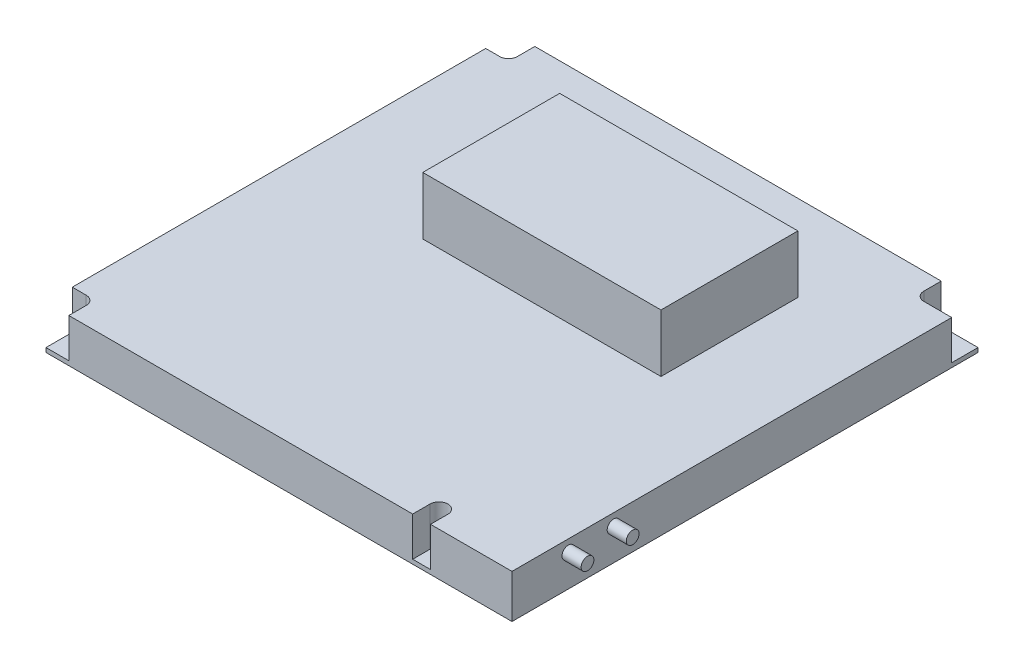
SolidWorks part; units mm, degrees
ref_plane "Front" through (0, 0, 0) normal (0, 0, 1) x (1, 0, 0)
ref_plane "Top" through (0, 0, 0) normal (0, 1, 0) x (1, 0, 0)
ref_plane "Right" through (0, 0, 0) normal (1, 0, 0) x (0, 0, -1)
sketch "Sketch1" plane through (0, 0, 0) normal (0, 1, 0) x (1, 0, 0)
  line L1 (-85.09, -85.09) -> (85.09, -85.09)
  line L2 (-85.09, -85.09) -> (-85.09, 85.09)
  line L3 (-85.09, 85.09) -> (85.09, 85.09)
  line L4 (85.09, -85.09) -> (85.09, 85.09)
  line L5 (-85.09, -85.09) -> (85.09, 85.09) construction
  line L6 (-85.09, 85.09) -> (85.09, -85.09) construction
  circle A0 centre (-80.01, 78.74) radius 1.975
  circle A1 centre (74.91, 78.74) radius 1.975
  circle A2 centre (-80.01, -78.74) radius 1.975
  circle A3 centre (52.07, -78.74) radius 1.975
  point P0 (0, 0)
  dimension "D3" = 6.35
  dimension "D4" = 5.08
  dimension "D5" = 3.95
  dimension "D6" = 6.35
  dimension "D7" = 10.18
  dimension "D8" = 3.95
  dimension "D9" = 3.95
  dimension "D10" = 6.35
  dimension "D11" = 5.08
  dimension "D12" = 33.02
  dimension "D13" = 6.35
  dimension "D14" = 3.95
  dimension "D1" = 170.18
  dimension "D2" = 170.18
extrude "Boss-Extrude1" add sketch "Sketch1" along normal blind 15.875
sketch "Sketch3" plane through (0, 15.875, 0) normal (0, 1, 0) x (1, 0, 0)
  line L0 (-76.7588, 78.74) -> (-76.7588, 85.09)
  line L1 (85.09, 85.09) -> (-85.09, 85.09) construction
  line L2 (-76.7588, 85.09) -> (-85.09, 85.09)
  line L3 (-85.09, 85.09) -> (-85.09, 75.4888)
  line L4 (-85.09, 85.09) -> (-85.09, -85.09) construction
  line L5 (-85.09, 75.4888) -> (-80.01, 75.4888)
  line L6 (71.6588, 78.74) -> (71.6588, 85.09)
  line L7 (71.6588, 85.09) -> (85.09, 85.09)
  line L8 (85.09, 85.09) -> (85.09, 75.4888)
  line L9 (85.09, -85.09) -> (85.09, 85.09) construction
  line L10 (85.09, 75.4888) -> (74.91, 75.4888)
  line L11 (48.8188, -78.74) -> (48.8188, -85.09)
  line L12 (-85.09, -85.09) -> (85.09, -85.09) construction
  line L13 (48.8188, -85.09) -> (55.3212, -85.09)
  line L14 (55.3212, -85.09) -> (55.3212, -78.74)
  line L15 (-80.01, -75.4888) -> (-85.09, -75.4888)
  line L16 (-85.09, -75.4888) -> (-85.09, -85.09)
  line L17 (-85.09, -85.09) -> (-76.7588, -85.09)
  line L18 (-76.7588, -85.09) -> (-76.7588, -78.74)
  arc A0 (-76.7588, -78.74) -> (-80.01, -75.4888) centre (-80.01, -78.74) ccw
  arc A1 (55.3212, -78.74) -> (48.8188, -78.74) centre (52.07, -78.74) ccw
  arc A2 (71.6588, 78.74) -> (74.91, 75.4888) centre (74.91, 78.74) ccw
  arc A3 (-80.01, 75.4888) -> (-76.7588, 78.74) centre (-80.01, 78.74) ccw
  dimension "D1" = 6.5024
  dimension "D2" = 6.5024
  dimension "D3" = 6.5024
  dimension "D4" = 6.5024
extrude "Cut-Extrude1" cut sketch "Sketch3" against normal offset from surface (14.3 mm away) 1.575 up to face at (-80.01, 0, 80.715)
sketch "Sketch4" plane through (0, 15.875, 0) normal (0, 1, 0) x (1, 0, 0)
  line L0 (-76.7588, -85.09) -> (48.8188, -85.09) construction
  line L1 (-36.331, 3.74) -> (50.669, 3.74)
  line L2 (-36.331, 3.74) -> (-36.331, 53.74)
  line L3 (-36.331, 53.74) -> (50.669, 53.74)
  line L4 (50.669, 3.74) -> (50.669, 53.74)
  line L5 (-36.331, 3.74) -> (50.669, 53.74) construction
  line L6 (-36.331, 53.74) -> (50.669, 3.74) construction
  line L7 (-85.09, 75.4888) -> (-85.09, -75.4888) construction
  line L8 (71.6588, 85.09) -> (-76.7588, 85.09) construction
  line L9 (85.09, -85.09) -> (85.09, 75.4888) construction
  point P0 (7.169, 28.74)
  dimension "D1" = 88.83
  dimension "D2" = 48.759
  dimension "D3" = 31.35
  dimension "D4" = 34.421
extrude "Boss-Extrude2" add sketch "Sketch4" along normal blind 21.049
sketch "Sketch5" plane through (85.09, 0, 0) normal (1, 0, 0) x (0, 0, -1)
  line L0 (-85.09, 0) -> (85.09, 0) construction
  line L1 (-85.09, 15.875) -> (-85.09, 0) construction
  circle A0 centre (-64.51, 11.575) radius 2.325
  circle A1 centre (-48.01, 11.575) radius 2.325
  dimension "D1" = 4.65
  dimension "D2" = 4.65
  dimension "D3" = 11.575
  dimension "D4" = 11.575
  dimension "D5" = 20.58
  dimension "D6" = 16.5
extrude "Boss-Extrude3" add sketch "Sketch5" along normal blind 7
